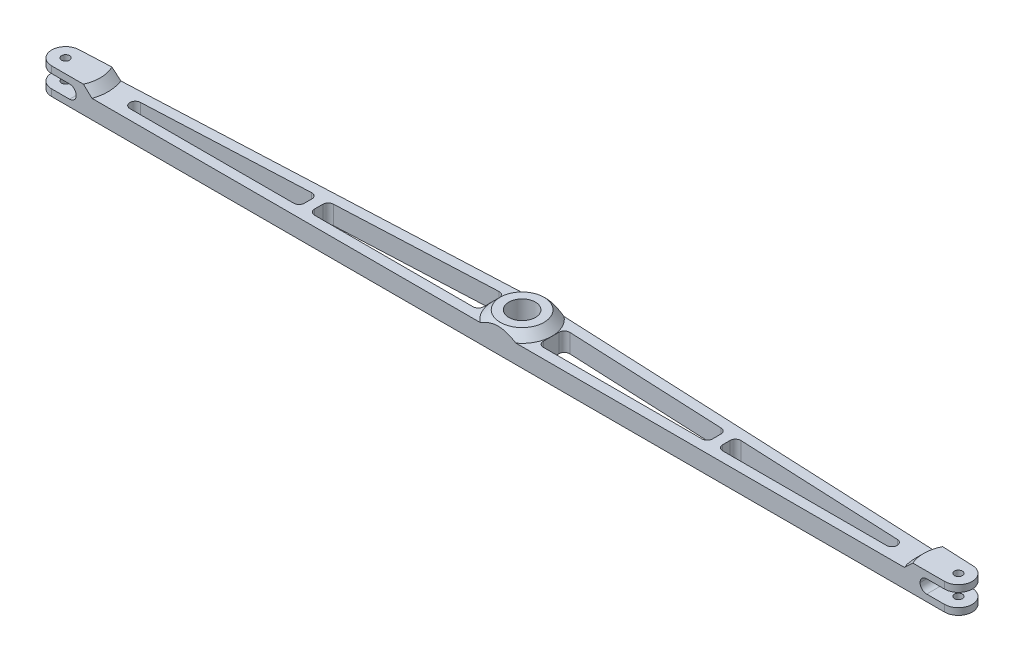
SolidWorks part; units mm, degrees
material "6061-T6 (SS)"
ref_plane "Front Plane" through (0, 0, 0) normal (0, 0, 1) x (1, 0, 0)
ref_plane "Top Plane" through (0, 0, 0) normal (0, 1, 0) x (1, 0, 0)
ref_plane "Right Plane" through (0, 0, 0) normal (1, 0, 0) x (0, 0, -1)
sketch "Sketch1" plane through (0, 0, 0) normal (0, 1, 0) x (1, 0, 0)
  line L0 (0, 0) -> (-266, -6.0325) construction
  line L1 (0, 0) -> (266, -6.0325) construction
  line L2 (-266, -6.0325) -> (266, -6.0325) construction
  line L3 (-266, -14.2875) -> (266, -14.2875)
  line L4 (-266.3742, 2.214) -> (-0.6477, 14.2728)
  line L5 (266.3742, 2.214) -> (0.6477, 14.2728)
  arc A1 (-266.3742, 2.214) -> (-266, -14.2875) centre (-266, -6.0325) ccw
  arc A2 (266, -14.2875) -> (266.3742, 2.214) centre (266, -6.0325) ccw
  arc A3 (0.6477, 14.2728) -> (-0.6477, 14.2728) centre (0, 0) ccw
  circle A4 centre (0, 0) radius 14.2875 construction
  circle A5 centre (-266, -6.0325) radius 2.3813
  circle A6 centre (266, -6.0325) radius 2.3813
  dimension "D2" = 28.575
  dimension "D3" = 4.7625
  dimension "D4" = 8.255
  dimension "D1" = 532
extrude "Boss-Extrude1" add sketch "Sketch1" along normal mid plane 15.875
sketch "Sketch3" plane through (0, 7.9375, 0) normal (0, 1, 0) x (1, 0, 0)
  circle A0 centre (0, 0) radius 7.9375
  dimension "D1" = 15.875
extrude "Cut-Extrude2" cut sketch "Sketch3" against normal up to next
sketch "Sketch2" plane through (0, 0, 0) normal (0, 0, 1) x (1, 0, 0)
  line L0 (274.255, -7.9375) -> (274.255, 7.9375) construction
  line L1 (251.395, -3.9375) -> (274.255, -3.9375)
  line L2 (251.395, -3.9375) -> (251.395, 3.9375)
  line L3 (251.395, 3.9375) -> (274.255, 3.9375)
  line L4 (274.255, -3.9375) -> (274.255, 3.9375)
  line L5 (251.395, -3.9375) -> (274.255, 3.9375) construction
  line L6 (251.395, 3.9375) -> (274.255, -3.9375) construction
  line L7 (274.255, 7.9375) -> (266, 7.9375) construction
  point P0 (262.825, 0)
  dimension "D1" = 4
  dimension "D2" = 22.86
extrude "Cut-Extrude1" cut sketch "Sketch2" against normal through all both and the other way through all
sketch "Sketch4" plane through (0, 7.9375, 0) normal (0, 1, 0) x (1, 0, 0)
  line L0 (17.78, 7.4892) -> (17.78, -8.2875)
  line L6 (17.78, 7.4892) -> (118.6065, 2.9136)
  line L7 (17.78, -8.2875) -> (118.6065, -8.2875)
  line L8 (124.6065, -8.2875) -> (225.4331, -8.2875)
  line L9 (124.6065, 2.6413) -> (225.577, -1.9408)
  line L10 (266.3742, 2.214) -> (0.6477, 14.2728) construction
  line L11 (118.6065, -8.2875) -> (118.6065, 2.9136)
  line L12 (124.6065, 2.6413) -> (124.6065, -8.2875)
  line L14 (118.6065, 2.9136) -> (118.8785, 8.9074) construction
  line L15 (118.6065, -8.2875) -> (118.6065, -14.2875) construction
  line L16 (-266, -14.2875) -> (266, -14.2875) construction
  line L17 (118.6065, -8.2875) -> (124.6065, -8.2875) construction
  arc A3 (225.577, -1.9408) -> (225.4331, -8.2875) centre (225.4331, -5.1125) cw
  dimension "D1" = 17.78
  dimension "D3" = 3.175
  dimension "D2" = 6
extrude "Cut-Extrude3" cut sketch "Sketch4" against normal up to next
sketch "Sketch7" plane through (0, 0, 0) normal (0, 0, 1) x (1, 0, 0)
  line L0 (225.4331, 7.9375) -> (225.4331, 3.1745)
  line L1 (-266, 7.9375) -> (266, 7.9375) construction
  line L2 (225.4331, 3.1745) -> (0, 3.1745)
  line L3 (0, 3.1745) -> (0, 7.9375)
  line L4 (0, 7.9375) -> (225.4331, 7.9375)
  dimension "D3" = 4.763
extrude "Cut-Extrude4" cut sketch "Sketch7" against normal through all both and the other way through all
ref_axis "Axis1" through (266, 7.9375, 6.0325) along (0, -1, 0)
ref_plane "Plane1" through (0, 0, 6.0325) normal (0, 0, 1) x (1, 0, 0)
sketch "Sketch10" plane through (0, 0, 6.0325) normal (0, 0, 1) x (1, 0, 0)
  line L0 (220.3531, 3.1745) -> (240.6, 3.1745)
  line L1 (240.6, 3.1745) -> (245.363, 7.9375)
  line L2 (225.4331, 7.9375) -> (266, 7.9375) construction
  line L3 (245.363, 7.9375) -> (220.3531, 7.9375)
  line L4 (220.3531, 7.9375) -> (220.3531, 3.1745)
  line L6 (266, 10.6134) -> (266, -0.6413) construction
  line L7 (266, 7.9375) -> (266, 3.9375) construction
  line L9 (225.4331, 3.1745) -> (225.4331, 7.9375) construction
  dimension "D1" = 45
  dimension "D2" = 25.4
  dimension "D3" = 5.08
revolve "Cut-Revolve2" cut sketch "Sketch10" angle 360 about L6
fillet "Fillet1" radius 3.175 6 edges at (17.78, -2.3815, 8.2875) (17.78, -2.3815, -7.4892) (118.6065, -2.3815, 8.2875) (118.6065, -2.3815, -2.9136) (124.6065, -2.3815, 8.2875) (124.6065, -2.3815, -2.6413)
fillet "Fillet2" radius 3.9688 2 edges at (251.395, -3.9375, 5.6969) (251.395, 3.9375, 5.6969)
mirror "Mirror1" about plane through (0, 0, 0) normal (1, 0, 0) of "Fillet2", "Cut-Extrude4", "Cut-Extrude1", "Cut-Extrude3", "Fillet1", "Cut-Revolve2"
sketch "Sketch8" plane through (0, 3.1745, 0) normal (0, 1, 0) x (1, 0, 0)
  line L1 (-13.0175, 3.4299) -> (-13.0175, -4.3052) construction
  line L2 (-17.78, -5.1125) -> (-17.78, 4.1668) construction
  circle A0 centre (0, 0) radius 13.0175
  circle A1 centre (0, 0) radius 7.9375 construction
  circle A2 centre (0, 0) radius 7.9375
  dimension "D1" = 4.7625
extrude "Boss-Extrude2" add sketch "Sketch8" along normal up to surface (4.763 mm away) up to face at (266, 7.9375, 8.4138)
chamfer "Chamfer2" distance 4.7625 angle 45 1 edges at (13.0175, 3.1745, 0)
